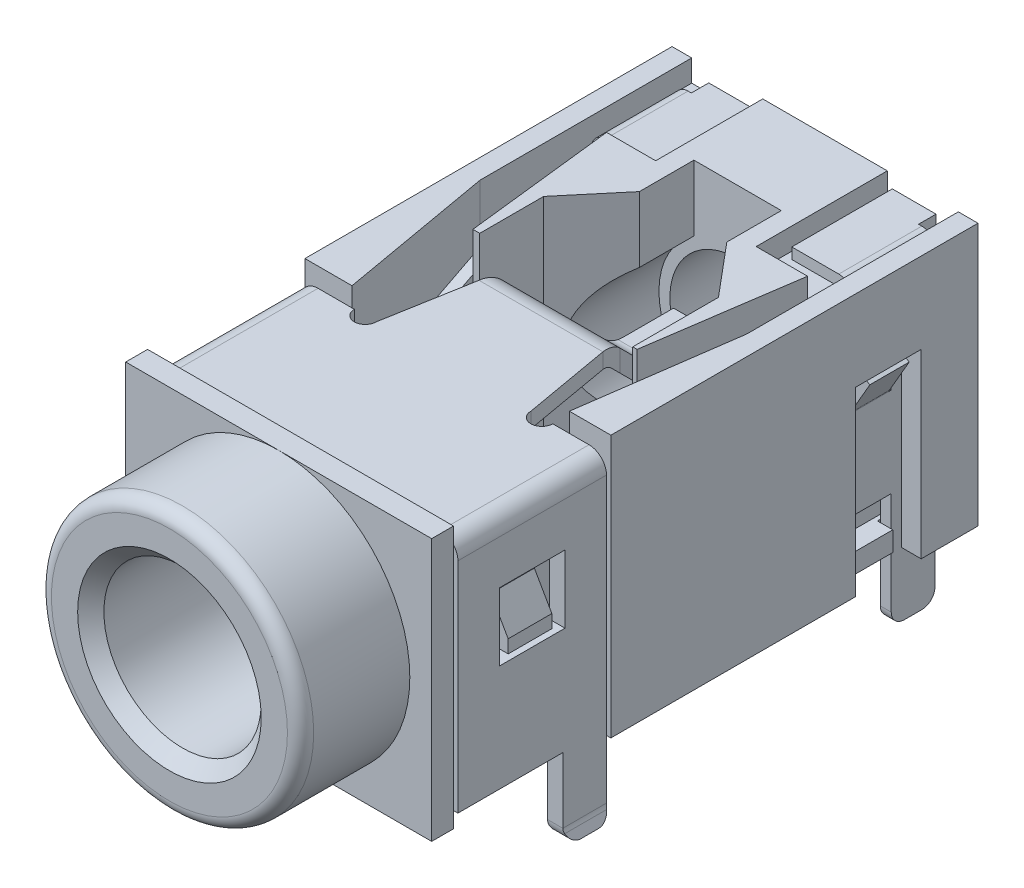
SolidWorks part; units mm, degrees
ref_plane "Front Plane" through (0, 0, 0) normal (0, 0, 1) x (1, 0, 0)
ref_plane "Top Plane" through (0, 0, 0) normal (0, 1, 0) x (1, 0, 0)
ref_plane "Right Plane" through (0, 0, 0) normal (1, 0, 0) x (0, 0, -1)
sketch "Sketch1" plane through (0, 0, 0) normal (0, 0, 1) x (1, 0, 0)
  line L0 (-3.5, -3) -> (0, -3)
  line L1 (0, 3) -> (-3.5, 3)
  line L2 (-3.5, 3) -> (-3.5, -3)
  line L3 (0, -3) -> (3.5, -3)
  line L4 (3.5, -3) -> (3.5, 3)
  line L5 (3.5, 3) -> (0, 3)
extrude "Boss-Extrude1" add sketch "Sketch1" against normal blind 0.5
sketch "Sketch2" plane through (0, 0, -0.5) normal (0, 0, -1) x (-1, 0, 0)
  line L0 (-3.05, -3) -> (-3.05, 2.3)
  line L1 (3.05, -3) -> (3.05, 2.3)
  line L2 (3.05, 2.3) -> (-3.05, 2.3)
  line L3 (-3.05, -3) -> (3.05, -3)
extrude "Boss-Extrude2" add sketch "Sketch2" along normal blind 3.6
sketch "Sketch3" plane through (0, 0, -4.1) normal (0, 0, -1) x (-1, 0, 0)
  line L0 (-3.5, -3) -> (-3.05, -3)
  line L1 (-3.5, 3) -> (-3.5, -3)
  line L2 (-3.5, 3) -> (-2.4227, 3)
  line L3 (2.55, 3) -> (3.5, 3)
  line L4 (3.5, -3) -> (3.5, 3)
  line L5 (3.05, -3) -> (3.5, -3)
  line L6 (-3.05, -3) -> (3.05, -3)
  line L7 (-2.4227, 3) -> (2.55, 3)
  point P8 (0, -3)
extrude "Boss-Extrude3" add sketch "Sketch3" along normal blind 8.4
sketch "Sketch4" plane through (0, 3, 0) normal (0, 1, 0) x (1, 0, 0)
  line L1 (2.6, 9.5) -> (2.6, 11.95)
  line L2 (2.6, 11.95) -> (2.7, 11.95)
  line L3 (2.7, 11.95) -> (2.7, 12.05)
  line L4 (2.7, 12.05) -> (3.05, 12.05)
  line L5 (3.05, 12.05) -> (3.05, 12.5)
  line L6 (3.05, 12.5) -> (1.425, 12.5)
  line L7 (1.425, 12.5) -> (1.425, 9.5)
  line L8 (1.425, 9.5) -> (2.6, 9.5)
  line L9 (-3.05, 12.5) -> (-3.05, 12.05)
  line L10 (-3.05, 12.05) -> (-2.7, 12.05)
  line L11 (-2.7, 12.05) -> (-2.7, 11.95)
  line L12 (-2.7, 11.95) -> (-2.5489, 11.95)
  line L13 (-2.5489, 11.95) -> (-2.5489, 10.05)
  line L14 (-2.5489, 10.05) -> (-1.425, 10.05)
  line L15 (-1.425, 10.05) -> (-1.425, 12.5)
  line L16 (-1.425, 12.5) -> (-3.05, 12.5)
extrude "Cut-Extrude1" cut sketch "Sketch4" against normal blind 0.5
sketch "Sketch5" plane through (0, 3, 0) normal (0, 1, 0) x (1, 0, 0)
  line L0 (-2.4227, 4.1) -> (-3.05, 7.6577)
  line L1 (2.55, 4.1) -> (-2.4227, 4.1)
  line L2 (3.05, 7.6577) -> (2.55, 4.1)
  line L3 (3.05, 12.05) -> (3.05, 7.6577)
  line L4 (2.7, 12.05) -> (3.05, 12.05)
  line L5 (2.7, 12.05) -> (2.7, 11.95)
  line L6 (2.7, 11.95) -> (2.6, 11.95)
  line L7 (2.6, 9.5) -> (2.6, 11.95)
  line L8 (2.1, 6.1) -> (2.6, 9.5)
  line L9 (2, 6.1) -> (2.1, 6.1)
  line L10 (2, 8.0616) -> (2, 6.1)
  line L11 (1, 9.2534) -> (2, 8.0616)
  line L12 (1, 9.2534) -> (1, 10.5)
  line L13 (1, 10.5) -> (-1, 10.5)
  line L14 (-1, 10.5) -> (-1, 9.2534)
  line L15 (-2, 8.0616) -> (-1, 9.2534)
  line L16 (-2, 6.6) -> (-2, 8.0616)
  line L17 (-2, 6.6) -> (-2.1568, 6.6)
  line L18 (-2.5489, 10.05) -> (-2.1568, 6.6)
  line L19 (-3.05, 7.6577) -> (-3.05, 12.05)
  line L20 (-2.7, 12.05) -> (-3.05, 12.05)
  line L21 (-2.7, 12.05) -> (-2.7, 11.95)
  line L22 (-2.7, 11.95) -> (-2.5489, 11.95)
  line L23 (-2.5489, 11.95) -> (-2.5489, 10.05)
extrude "Cut-Extrude2" cut sketch "Sketch5" against normal blind 5.55
sketch "Sketch6" plane through (0, -3, 0) normal (0, -1, 0) x (1, 0, 0)
  line L0 (-3.05, -11.2) -> (-3.5, -11.2)
  line L1 (-3.05, -11.2) -> (-3.05, -12.05)
  line L2 (-2.7, -12.05) -> (-3.05, -12.05)
  line L3 (-2.7, -12.05) -> (-2.7, -11)
  line L4 (-3.05, -11) -> (-2.7, -11)
  line L5 (-3.05, -9.7) -> (-3.05, -11)
  line L6 (-3.5, -9.7) -> (-3.05, -9.7)
  line L7 (3.5, -11.2) -> (3.05, -11.2)
  line L8 (3.05, -12.05) -> (3.05, -11.2)
  line L9 (3.05, -12.05) -> (2.7, -12.05)
  line L10 (2.7, -11) -> (2.7, -12.05)
  line L11 (2.7, -11) -> (3.05, -11)
  line L12 (3.05, -11) -> (3.05, -9.7)
  line L13 (3.05, -9.7) -> (3.5, -9.7)
  line L14 (-3.5, -11.2) -> (-3.5, -9.7)
  line L15 (3.5, -11.2) -> (3.5, -9.7)
extrude "Cut-Extrude3" cut sketch "Sketch6" against normal blind 4.15
sketch "Sketch7" plane through (0, -3, 0) normal (0, -1, 0) x (1, 0, 0)
  line L0 (0.54, -12.5) -> (0.54, -12.025)
  line L1 (-0.51, -12.025) -> (-0.51, -12.5)
  line L2 (0.54, -12.025) -> (-0.51, -12.025)
  line L3 (1.75, -8.525) -> (0.9, -8.525)
  line L4 (1.75, -9.675) -> (1.75, -8.525)
  line L5 (0.9, -9.675) -> (1.75, -9.675)
  line L6 (0.9, -8.525) -> (0.9, -9.675)
  line L7 (-1.75, -8.525) -> (-1.75, -9.675)
  line L8 (-0.9, -8.525) -> (-1.75, -8.525)
  line L9 (-0.9, -9.675) -> (-0.9, -8.525)
  line L10 (-1.75, -9.675) -> (-0.9, -9.675)
  line L11 (-0.51, -12.5) -> (0.54, -12.5)
extrude "Cut-Extrude4" cut sketch "Sketch7" against normal blind 0.45
sketch "Sketch8" plane through (0, -3, 0) normal (0, -1, 0) x (1, 0, 0)
  line L0 (0.9, -8.525) -> (0.9, -9.675) construction
  line L1 (0.9, -9.675) -> (1.75, -9.675) construction
  line L2 (1.75, -9.675) -> (1.75, -8.525) construction
  line L3 (1.75, -8.525) -> (0.9, -8.525) construction
  line L4 (-0.9, -8.525) -> (-1.75, -8.525) construction
  line L5 (-1.75, -8.525) -> (-1.75, -9.675) construction
  line L6 (-1.75, -9.675) -> (-0.9, -9.675) construction
  line L7 (-0.9, -9.675) -> (-0.9, -8.525) construction
  line L8 (0.9, -8.525) -> (0.9, -9.675)
  line L9 (0.9, -9.675) -> (1.75, -9.675)
  line L10 (1.75, -9.675) -> (1.75, -8.525)
  line L11 (1.75, -8.525) -> (0.9, -8.525)
  line L12 (-0.9, -8.525) -> (-1.75, -8.525)
  line L13 (-1.75, -8.525) -> (-1.75, -9.675)
  line L14 (-1.75, -9.675) -> (-0.9, -9.675)
  line L15 (-0.9, -9.675) -> (-0.9, -8.525)
extrude "Cut-Extrude5" cut sketch "Sketch8" against normal blind 0.95
sketch "Sketch9" plane through (0, 0, -12.5) normal (0, 0, -1) x (-1, 0, 0)
  line L0 (1.75, -2.05) -> (1.75, -2.55)
  line L1 (1.75, -2.55) -> (0.54, -2.55)
  line L17 (-0.51, -2.55) -> (-1.75, -2.55)
  line L18 (-1.75, -2.55) -> (-1.75, -2.05)
  line L19 (-1.75, -2.05) -> (-1.2, -2.05)
  line L20 (-1.2, -2.05) -> (-1.2, -1.35)
  line L21 (-1.2, -1.35) -> (-0.7616, -1.35)
  line L22 (0.7616, -1.35) -> (1.2, -1.35)
  line L23 (1.2, -1.35) -> (1.2, -2.05)
  line L24 (1.2, -2.05) -> (1.75, -2.05)
  line L25 (-0.51, -2.55) -> (0.54, -2.55)
  arc A0 (-1.55, 0) -> (-0.7616, -1.35) centre (0, 0) ccw
  arc A1 (1.55, 0) -> (-1.55, 0) centre (0, 0) ccw
  arc A2 (0.7616, -1.35) -> (1.55, 0) centre (0, 0) ccw
extrude "Cut-Extrude6" cut sketch "Sketch9" against normal blind 8.4
sketch "Sketch10" plane through (0, -3, 0) normal (0, -1, 0) x (1, 0, 0)
  circle A4 centre (0, -2) radius 0.475
  circle A5 centre (0, -9) radius 0.475
extrude "Boss-Extrude4" add sketch "Sketch10" along normal blind 0.8
fillet "Fillet1" radius 0.2 2 edges at (0, -3.8, -9.475) (0, -3.8, -2.475)
ref_plane "Plane1" through (0, 0, -1.8) normal (0, 0, 1) x (1, 0, 0)
sketch "Sketch11" plane through (0, 0, -1.8) normal (0, 0, 1) x (1, 0, 0)
  line L0 (-3.45, -0.2096) -> (-3.05, -0.2096)
  line L1 (-3.05, -0.2096) -> (-3.05, 0.7904)
  line L2 (-3.05, 0.7904) -> (-3.45, 0.0904)
  line L3 (-3.45, 0.0904) -> (-3.45, -0.2096)
  line L4 (3.05, -0.2096) -> (3.45, -0.2096)
  line L5 (3.45, -0.2096) -> (3.45, 0.0904)
  line L6 (3.45, 0.0904) -> (3.05, 0.7904)
  line L7 (3.05, 0.7904) -> (3.05, -0.2096)
extrude "Boss-Extrude5" add sketch "Sketch11" against normal blind 1
sketch "Sketch12" plane through (0, 0, 0) normal (0, 0, 1) x (1, 0, 0)
  circle A2 centre (0, 0) radius 3
extrude "Boss-Extrude6" add sketch "Sketch12" along normal blind 2.5
sketch "Sketch13" plane through (0, 0, 2.5) normal (0, 0, 1) x (1, 0, 0)
  circle A2 centre (0, 0) radius 1.8
extrude "Cut-Extrude7" cut sketch "Sketch13" against normal up to surface (13 mm away) up to face at (0, 2.1836, -10.5)
fillet "Fillet2" radius 0.3 1 edges at (3, 0, 2.5)
chamfer "Chamfer1" distance 0.3 angle 45 1 edges at (1.8, 0, 2.5)
ref_plane "Plane2" through (0, 0, -0.6) normal (0, 0, 1) x (1, 0, 0)
sketch "Sketch15" plane through (0, 0, -0.6) normal (0, 0, 1) x (1, 0, 0)
  line L0 (-3.5, -2.44) -> (-3.5, -2.74)
  line L1 (-3.5, -2.74) -> (-3.15, -2.74)
  line L2 (-3.15, -2.74) -> (-3.15, -2.44)
  line L3 (3.15, -2.74) -> (3.5, -2.74)
  line L4 (3.5, -2.74) -> (3.5, -2.44)
  line L5 (3.15, -2.44) -> (3.15, -2.74)
  line L6 (-3.15, -2.44) -> (-3.15, 2.26)
  line L7 (-3.1, 2.31) -> (3.1, 2.31)
  line L8 (3.15, 2.26) -> (3.15, -2.44)
  line L9 (3.5, -2.44) -> (3.5, 2.26)
  line L10 (3.1, 2.66) -> (-3.1, 2.66)
  line L11 (-3.5, 2.26) -> (-3.5, -2.44)
  arc A0 (-3.1, 2.31) -> (-3.15, 2.26) centre (-3.1, 2.26) ccw
  arc A1 (3.15, 2.26) -> (3.1, 2.31) centre (3.1, 2.26) ccw
  arc A2 (3.5, 2.26) -> (3.1, 2.66) centre (3.1, 2.26) ccw
  arc A3 (-3.1, 2.66) -> (-3.5, 2.26) centre (-3.1, 2.26) ccw
extrude "Boss-Extrude7" add sketch "Sketch15" against normal blind 3.4 separate body
sketch "Sketch16" plane through (0, 0, -4) normal (0, 0, -1) x (-1, 0, 0)
  line L0 (3.15, -2.74) -> (3.15, -4.24)
  line L1 (3.2062, -4.4936) -> (3.2279, -4.54)
  line L2 (3.2279, -4.54) -> (3.614, -4.54)
  line L3 (3.614, -4.54) -> (3.5234, -4.3457)
  line L4 (3.5, -4.24) -> (3.5, -2.74)
  line L5 (3.5, -2.74) -> (3.15, -2.74)
  line L7 (-3.5, -2.74) -> (-3.15, -2.74)
  line L8 (-3.5, -4.24) -> (-3.5, -2.74)
  line L9 (-3.614, -4.54) -> (-3.5234, -4.3457)
  line L10 (-3.2279, -4.54) -> (-3.614, -4.54)
  line L11 (-3.2062, -4.4936) -> (-3.2279, -4.54)
  line L12 (-3.15, -2.74) -> (-3.15, -4.24)
  arc A0 (3.15, -4.24) -> (3.2062, -4.4936) centre (3.75, -4.24) ccw
  arc A1 (3.5, -4.24) -> (3.5234, -4.3457) centre (3.75, -4.24) ccw
  arc A2 (-3.5, -4.24) -> (-3.5234, -4.3457) centre (-3.75, -4.24) cw
  arc A3 (-3.15, -4.24) -> (-3.2062, -4.4936) centre (-3.75, -4.24) cw
  point P10 (3.15, -2.74)
  point P24 (-3.15, -2.74)
extrude "Boss-Extrude8" add sketch "Sketch16" against normal blind 1
sketch "Sketch17" plane through (3.15, 0, 0) normal (-1, 0, 0) x (0, 0, 1)
  line L0 (-3.05, -0.2996) -> (-1.55, -0.2996)
  line L1 (-3.05, 1.2504) -> (-3.05, -0.2996)
  line L2 (-1.55, 1.2504) -> (-3.05, 1.2504)
  line L3 (-1.55, -0.2996) -> (-1.55, 1.2504)
extrude "Cut-Extrude8" cut sketch "Sketch17" against normal blind 0.35
mirror "Mirror1" about plane through (0, 0, 0) normal (1, 0, 0) of "Cut-Extrude8"
sketch "Sketch18" plane through (0, 0, 0) normal (1, 0, 0) x (0, 0, -1)
  line L7 (4, 2.66) -> (4, 2.31)
  line L10 (8.3265, 0.6027) -> (6.4596, 2.4696)
  line L11 (6.2121, 2.2221) -> (8.079, 0.3552)
  line L12 (8.6484, 0.1502) -> (9.834, 0.1502)
  line L13 (9.834, 0.5002) -> (8.6484, 0.5002)
  line L14 (9.834, 0.1502) -> (9.834, 0.5002)
  line L15 (8.6484, 0.5002) -> (8.574, 0.5002)
  line L16 (8.574, 0.1502) -> (8.6484, 0.1502)
  line L17 (4, 2.66) -> (6, 2.66)
  line L18 (4, 2.31) -> (6, 2.31)
  arc A4 (6, 2.66) -> (6.4596, 2.4696) centre (6, 2.01) cw
  arc A5 (6, 2.31) -> (6.2121, 2.2221) centre (6, 2.01) cw
  arc A6 (8.574, 0.5002) -> (8.3265, 0.6027) centre (8.574, 0.8502) cw
  arc A7 (8.574, 0.1502) -> (8.079, 0.3552) centre (8.574, 0.8502) cw
  point P0 (4, 2.66)
extrude "Boss-Extrude9" add sketch "Sketch18" along normal mid plane 3.54
sketch "Sketch19" plane through (0, 2.66, 0) normal (0, 1, 0) x (1, 0, 0)
  line L0 (-0.8, 9.834) -> (0.8, 9.834)
  line L1 (0.8, 9.834) -> (0.8, 8.6484)
  line L2 (-0.8, 8.6484) -> (-0.8, 9.834)
  line L3 (1.3514, 6.4596) -> (0.8858, 8.3265)
  line L4 (-0.8858, 8.3265) -> (-1.3514, 6.4596)
  line L5 (-1.4171, 6) -> (-1.7698, 4)
  line L6 (-2.2698, 4) -> (-2.2698, 10.0311)
  line L7 (1.7698, 4) -> (1.4171, 6)
  line L8 (-2.2698, 10.0311) -> (2.2698, 10.0311)
  line L9 (2.2698, 10.0311) -> (2.2698, 4)
  line L10 (-0.8131, 8.574) -> (-0.8, 8.6484)
  line L11 (0.8131, 8.574) -> (0.8, 8.6484)
  arc A0 (-2.2698, 4) -> (-2.0198, 3.75) centre (-2.0198, 4) ccw
  arc A1 (-2.0198, 3.75) -> (-1.7698, 4) centre (-2.0198, 4) ccw
  arc A2 (2.0198, 3.75) -> (2.2698, 4) centre (2.0198, 4) ccw
  arc A3 (1.7698, 4) -> (2.0198, 3.75) centre (2.0198, 4) ccw
  spline S0 degree 3 poles (-0.8131, 8.574) (-0.8374, 8.4824) (-0.8616, 8.3913) (-0.8858, 8.3265) knots 0 0 0 0 1 1 1 1
  spline S1 degree 3 poles (0.8858, 8.3265) (0.8616, 8.3913) (0.8374, 8.4824) (0.8131, 8.574) knots 0 0 0 0 1 1 1 1
  spline S2 degree 3 poles (1.4171, 6) (1.4116, 6.0427) (1.4006, 6.128) (1.3843, 6.2503) (1.3679, 6.3631) (1.3569, 6.4294) (1.3514, 6.4596) knots 0 0 0 0 0.25 0.5 0.75 1 1 1 1 weights 1 1 1 1 1 1 1
  spline S3 degree 3 poles (-1.3514, 6.4596) (-1.3569, 6.4294) (-1.3679, 6.3631) (-1.3843, 6.2503) (-1.4006, 6.128) (-1.4116, 6.0427) (-1.4171, 6) knots 0 0 0 0 0.25 0.5 0.75 1 1 1 1 weights 1 1 1 1 1 1 1
extrude "Cut-Extrude9" cut sketch "Sketch19" against normal blind 3
fillet "Fillet3" radius 0.3 4 edges at (-3.421, -4.54, -3) (-3.421, -4.54, -4) (3.421, -4.54, -4) (3.421, -4.54, -3)
ref_plane "Plane3" through (0, 0, -12.04) normal (0, 0, -1) x (-1, 0, 0)
sketch "Sketch20" plane through (0, 0, -12.04) normal (0, 0, -1) x (-1, 0, 0)
  line L0 (2.725, 2.46) -> (2.975, 2.46)
  line L4 (2.725, 2.46) -> (2.725, -4.54)
  line L5 (2.725, -4.54) -> (2.975, -4.54)
  line L6 (2.975, -4.54) -> (2.975, 2.46)
extrude "Boss-Extrude10" add sketch "Sketch20" against normal blind 2.4 separate body
sketch "Sketch21" plane through (-2.975, 0, 0) normal (-1, 0, 0) x (0, 0, 1)
  line L0 (-9.64, -1.89) -> (-11.04, -1.89)
  line L1 (-11.04, -4.54) -> (-11.04, -1.89)
  line L2 (-11.04, -4.54) -> (-9.64, -4.54)
  line L3 (-9.64, -4.54) -> (-9.64, -1.89)
  line L4 (-11.04, 0.16) -> (-10.99, 0.16)
  line L5 (-10.99, 0.16) -> (-10.09, 0.16)
  line L6 (-10.09, 0.16) -> (-10.04, 0.16)
  line L7 (-11.04, 1.36) -> (-11.04, 0.16)
  line L8 (-10.04, 1.36) -> (-11.04, 1.36)
  line L9 (-10.04, 0.16) -> (-10.04, 1.36)
extrude "Cut-Extrude10" cut sketch "Sketch21" against normal blind 0.25
sketch "Sketch23" plane through (0, 2.46, 0) normal (0, 1, 0) x (1, 0, 0)
  line L0 (-1.5393, 3.6222) -> (-1.4336, 3.3956)
  line L1 (-1.3355, 4.5171) -> (-1.9908, 4.976)
  line L2 (-2.1342, 4.7712) -> (-1.4789, 4.3124)
  line L3 (-2.1965, 5.2988) -> (-2.7174, 8.2532)
  line L4 (-2.9636, 8.2098) -> (-2.4427, 5.2553)
  line L5 (-2.725, 8.34) -> (-2.725, 9.64)
  line L6 (-2.725, 9.64) -> (-2.975, 9.64)
  line L7 (-2.975, 9.64) -> (-2.975, 8.34)
  arc A0 (-1.5393, 3.6222) -> (-1.4789, 4.3124) centre (-1.7083, 3.9847) ccw
  arc A1 (-1.4336, 3.3956) -> (-1.3355, 4.5171) centre (-1.7083, 3.9847) ccw
  arc A2 (-2.1965, 5.2988) -> (-1.9908, 4.976) centre (-1.7041, 5.3856) ccw
  arc A3 (-2.4427, 5.2553) -> (-2.1342, 4.7712) centre (-1.7041, 5.3856) ccw
  arc A4 (-2.975, 8.34) -> (-2.9636, 8.2098) centre (-2.225, 8.34) ccw
  ellipse E0 centre (-2.1788, 8.3443) end of major axis (-2.7228, 8.2932) minor radius 0.5228 (-2.725, 8.34) -> (-2.7174, 8.2532) ccw
  point P24 (-2.975, 9.64)
extrude "Boss-Extrude11" add sketch "Sketch23" against normal up to surface (4.35 mm away) up to face at (-2.85, -1.89, -10.34)
sketch "Sketch24" plane through (-2.975, 0, 0) normal (-1, 0, 0) x (0, 0, 1)
  line L0 (-9.64, -1.865) -> (-8.34, -1.6451)
  line L1 (-8.2098, -1.6267) -> (-5.2553, -1.1193)
  line L2 (-4.7712, -1.0363) -> (-4.3124, -0.901)
  line L3 (-4.3124, 1.0518) -> (-4.7712, 1.246)
  line L4 (-5.2553, 1.3651) -> (-8.2098, 2.0931)
  line L5 (-8.34, 2.1195) -> (-9.64, 2.435)
  line L6 (-9.64, -1.865) -> (-9.64, -2.1316)
  line L7 (-9.64, -2.1316) -> (-3.3956, -2.1316)
  line L8 (-3.3956, -2.1316) -> (-3.3956, -0.715)
  line L9 (-3.3956, 0.785) -> (-3.3956, 2.6527)
  line L10 (-3.3956, 2.6527) -> (-9.64, 2.6527)
  line L11 (-9.64, 2.6527) -> (-9.64, 2.435)
  line L12 (-2.0956, 0.785) -> (-3.3956, 0.785) construction
  line L13 (-3.3956, -1.89) -> (-3.3956, 2.46) construction
  spline S0 degree 3 poles (-8.34, -1.6451) (-8.2964, -1.639) (-8.2527, -1.6328) (-8.2098, -1.6267) knots 0 0 0 0 1 1 1 1 weights 1 1 1 1
  spline S1 degree 3 poles (-5.2553, -1.1193) (-5.2067, -1.1123) (-5.1114, -1.0984) (-4.98, -1.0778) (-4.8641, -1.0571) (-4.7995, -1.0432) (-4.7712, -1.0363) knots 0 0 0 0 0.25 0.5 0.75 1 1 1 1 weights 1 1 1 1 1 1 1
  spline S2 degree 3 poles (-4.3124, -0.901) (-4.2945, -0.8941) (-4.253, -0.8803) (-4.1762, -0.8596) (-4.0855, -0.8381) (-4.0196, -0.8235) (-3.9847, -0.8157) knots 0 0 0 0 0.111111 0.222222 0.333333 0.458197 0.458197 0.458197 0.458197 weights 1 1 1 1 1 1 1
  spline S3 degree 3 poles (-3.3956, -0.715) (-3.4148, -0.7212) (-3.4617, -0.7336) (-3.5545, -0.7521) (-3.6661, -0.7706) (-3.7919, -0.7892) (-3.9008, -0.8043) (-3.9656, -0.8131) (-3.9847, -0.8157) knots 0 0 0 0 0.1 0.2 0.3 0.4 0.5 0.541821 0.541821 0.541821 0.541821 weights 1 1 1 1 1 1 1 1 1
  spline S4 degree 3 poles (-3.3956, 0.785) (-3.4144, 0.7937) (-3.4603, 0.8112) (-3.5523, 0.8376) (-3.6638, 0.8643) (-3.7903, 0.8911) (-3.8999, 0.9129) (-3.9653, 0.9257) (-3.9847, 0.9295) knots 0 0 0 0 0.1 0.2 0.3 0.4 0.5 0.542086 0.542086 0.542086 0.542086 weights 1 1 1 1 1 1 1 1 1
  spline S5 degree 3 poles (-3.9847, 0.9295) (-3.9886, 0.9308) (-4.0235, 0.9419) (-4.0891, 0.9629) (-4.1762, 0.9925) (-4.253, 1.0221) (-4.2945, 1.0419) (-4.3124, 1.0518) knots 0.541711 0.541711 0.541711 0.541711 0.555556 0.666667 0.777778 0.888889 1 1 1 1 weights 1 1 1 1 1 1 1 1
  spline S6 degree 3 poles (-4.7712, 1.246) (-4.7995, 1.2559) (-4.8641, 1.2759) (-4.98, 1.3055) (-5.1114, 1.3352) (-5.2067, 1.3551) (-5.2553, 1.3651) knots 0 0 0 0 0.25 0.5 0.75 1 1 1 1 weights 1 1 1 1 1 1 1
  spline S7 degree 3 poles (-8.2098, 2.0931) (-8.2527, 2.1019) (-8.2964, 2.1107) (-8.34, 2.1195) knots 0 0 0 0 1 1 1 1 weights 1 1 1 1
  point P18 (-9.64, 2.435)
extrude "Cut-Extrude11" cut sketch "Sketch24" against normal blind 2
sketch "Sketch25" plane through (0, 0, -12.04) normal (0, 0, -1) x (-1, 0, 0)
  line L1 (2.6, 2.76) -> (1.6, 2.76)
  line L2 (1.6, 2.76) -> (1.6, 2.51)
  line L3 (1.6, 2.51) -> (2.6, 2.51)
  line L4 (2.675, 2.76) -> (2.6, 2.76)
  line L6 (2.6, 2.51) -> (2.675, 2.51)
  line L7 (2.725, 2.46) -> (2.975, 2.46)
  arc A0 (2.975, 2.46) -> (2.675, 2.76) centre (2.675, 2.46) ccw
  arc A1 (2.725, 2.46) -> (2.675, 2.51) centre (2.675, 2.46) ccw
  point P12 (2.725, 2.46)
extrude "Boss-Extrude12" add sketch "Sketch25" against normal blind 1.9
sketch "Sketch26" plane through (0, 0, -12.04) normal (0, 0, -1) x (-1, 0, 0)
  line L1 (2.6, 2.76) -> (1.6, 2.76)
  line L2 (1.6, 2.76) -> (1.6, 2.51)
  line L3 (1.6, 2.51) -> (2.6, 2.51)
  line L5 (2.6, 2.76) -> (2.6, 2.51)
  point P4 (1.6, 2.51)
extrude "Boss-Extrude13" add sketch "Sketch26" along normal blind 0.4
ref_plane "Plane4" through (0, 0, -10.54) normal (0, 0, -1) x (-1, 0, 0)
sketch "Sketch27" plane through (0, 0, -10.54) normal (0, 0, -1) x (-1, 0, 0)
  line L4 (2.725, 0.16) -> (2.975, 0.16) construction
  line L6 (3.4359, 0.9717) -> (2.9817, 0.185)
  line L7 (3.2194, 1.0967) -> (3.4359, 0.9717)
  line L8 (2.7652, 0.31) -> (3.2194, 1.0967)
  line L9 (2.725, 0.16) -> (2.975, 0.16)
  arc A2 (2.975, 0.16) -> (2.9817, 0.185) centre (3.025, 0.16) cw
  arc A3 (2.725, 0.16) -> (2.7652, 0.31) centre (3.025, 0.16) cw
extrude "Boss-Extrude14" add sketch "Sketch27" along normal mid plane 0.9
fillet "Fillet4" radius 0.3 2 edges at (-2.85, -4.54, -11.04) (-2.85, -4.54, -12.04)
mirror "Mirror2" about plane through (0, 0, 0) normal (1, 0, 0) of bodies 126
sketch "Sketch28" plane through (0, 0, 0) normal (1, 0, 0) x (0, 0, -1)
  line L17 (12.175, -4.54) -> (12.175, -2.59)
  line L18 (12.425, -4.54) -> (12.175, -4.54)
  line L19 (12.425, -2.59) -> (12.425, -4.54)
  line L20 (9.525, -2.29) -> (12.125, -2.29)
  line L21 (12.125, -2.54) -> (9.525, -2.54)
  line L22 (8.425, -2.29) -> (9.525, -2.29)
  line L23 (9.525, -2.54) -> (8.425, -2.54)
  line L24 (7.425, -2.29) -> (8.425, -2.29)
  line L25 (8.425, -2.54) -> (7.425, -2.54)
  line L26 (4.3373, -1.1854) -> (7.3224, -2.2719)
  line L27 (7.2369, -2.5068) -> (4.2518, -1.4204)
  line L28 (2.6788, -0.5818) -> (4.3373, -1.1854)
  line L29 (1.9524, -1.1155) -> (1.7175, -1.03)
  line L30 (4.2518, -1.4204) -> (2.5933, -0.8167)
  arc A6 (12.125, -2.29) -> (12.425, -2.59) centre (12.125, -2.59) cw
  arc A7 (12.125, -2.54) -> (12.175, -2.59) centre (12.125, -2.59) cw
  arc A8 (7.425, -2.29) -> (7.3224, -2.2719) centre (7.425, -1.99) cw
  arc A9 (7.425, -2.54) -> (7.2369, -2.5068) centre (7.425, -1.99) cw
  arc A10 (1.7175, -1.03) -> (2.6788, -0.5818) centre (2.4222, -1.2865) cw
  arc A11 (1.9524, -1.1155) -> (2.5933, -0.8167) centre (2.4222, -1.2865) cw
extrude "Boss-Extrude15" add sketch "Sketch28" along normal mid plane 3.2 separate body
sketch "Sketch29" plane through (0, -2.29, 0) normal (0, 1, 0) x (1, 0, 0)
  line L0 (0.9, 12.125) -> (1.6, 12.125)
  line L1 (0.5, 12.125) -> (0.5, 12.425)
  line L2 (-1.6, 12.125) -> (-0.9, 12.125)
  line L3 (-0.5, 12.425) -> (-0.5, 12.125)
  line L4 (-1.6, 12.125) -> (-1.6, 12.425)
  line L5 (-1.6, 12.425) -> (-0.5, 12.425)
  line L6 (0.5, 12.425) -> (1.6, 12.425)
  line L7 (1.6, 12.425) -> (1.6, 12.125)
  line L8 (1, 9.525) -> (0.9, 9.525)
  line L9 (0.9, 9.525) -> (0.9, 8.425)
  line L10 (0.9, 8.425) -> (1.6, 8.425)
  line L11 (-1.6, 8.425) -> (-0.9, 8.425)
  line L12 (-0.9, 9.525) -> (-1, 9.525)
  line L13 (-0.9, 8.425) -> (-0.9, 9.525)
  line L14 (-1, 9.525) -> (-1.6, 9.525)
  line L15 (-1.6, 9.525) -> (-1.6, 8.425)
  line L16 (1, 9.525) -> (1.6, 9.525)
  line L17 (1.6, 9.525) -> (1.6, 8.425)
  arc A0 (0.7, 11.925) -> (0.9, 12.125) centre (0.7, 12.125) ccw
  arc A1 (0.5, 12.125) -> (0.7, 11.925) centre (0.7, 12.125) ccw
  arc A2 (-0.9, 12.125) -> (-0.7, 11.925) centre (-0.7, 12.125) ccw
  arc A3 (-0.7, 11.925) -> (-0.5, 12.125) centre (-0.7, 12.125) ccw
  point P26 (-1.6, 12.425)
extrude "Cut-Extrude12" cut sketch "Sketch29" against normal blind 2.25
sketch "Sketch30" plane through (0, -2.54, 0) normal (0, -1, 0) x (1, 0, 0)
  line L0 (0.8374, -1.7175) -> (-0.8374, -1.7175)
  line L1 (-0.8374, -1.7175) -> (-0.8374, -2.6788)
  line L2 (0.8374, -2.6788) -> (0.8374, -1.7175)
  line L3 (-0.8374, -4.3373) -> (-0.8374, -2.6788)
  line L4 (0.8374, -2.6788) -> (0.8374, -4.3373)
  line L5 (1.3975, -7.3224) -> (0.8374, -4.3373)
  line L6 (-0.8374, -4.3373) -> (-1.3975, -7.3224)
  line L7 (-1.4237, -7.425) -> (-1.6, -8.425)
  line L8 (1.6, -8.425) -> (1.4237, -7.425)
  line L9 (-1.6, -8.425) -> (-1.9081, -8.425)
  line L10 (-1.9081, -8.425) -> (-1.9081, -1.5328)
  line L11 (-1.9081, -1.5328) -> (1.8759, -1.5328)
  line L12 (1.8759, -1.5328) -> (2.0328, -8.425)
  line L13 (2.0328, -8.425) -> (1.6, -8.425)
  spline S0 degree 3 poles (1.4237, -7.425) (1.415, -7.3901) (1.4062, -7.3552) (1.3975, -7.3224) knots 0 0 0 0 1 1 1 1 weights 1 1 1 1
  spline S1 degree 3 poles (-1.3975, -7.3224) (-1.4062, -7.3552) (-1.415, -7.3901) (-1.4237, -7.425) knots 0 0 0 0 1 1 1 1 weights 1 1 1 1
  point P12 (1.6, -8.425)
extrude "Cut-Extrude13" cut sketch "Sketch30" against normal blind 2.25
